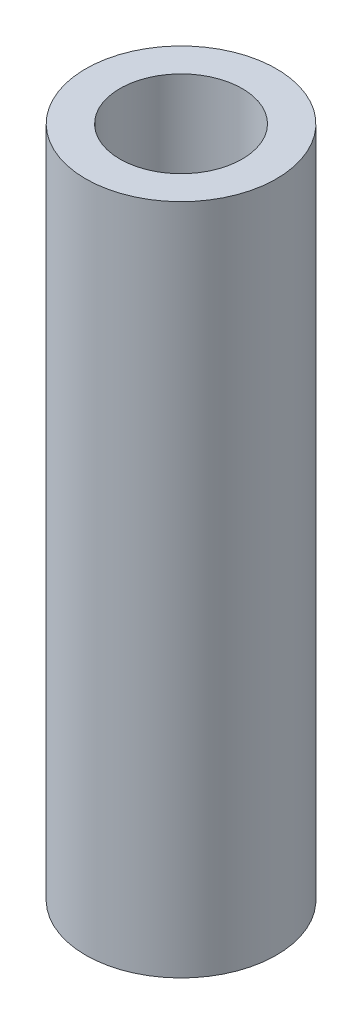
SolidWorks part; units mm, degrees
material "ABS"
ref_plane "Front Plane" through (0, 0, 0) normal (0, 0, 1) x (1, 0, 0)
ref_plane "Top Plane" through (0, 0, 0) normal (0, 1, 0) x (1, 0, 0)
ref_plane "Right Plane" through (0, 0, 0) normal (1, 0, 0) x (0, 0, -1)
sketch "Sketch1" plane through (0, 0, 0) normal (0, 1, 0) x (1, 0, 0)
  circle A0 centre (0, 0) radius 17.875
  circle A1 centre (0, 0) radius 27.875
  dimension "D1" = 35.75
  dimension "D2" = 55.75
extrude "Boss-Extrude1" add sketch "Sketch1" along normal blind 196.5
sketch "Sketch2" plane through (0, 0, 0) normal (1, 0, 0) x (0, 0, -1)
  line L0 (17.875, 196.5) -> (-17.875, 196.5) construction
  circle A0 centre (0, 131.8) radius 9.94
  circle A1 centre (0, 80.8) radius 9.94
  circle A2 centre (0, 29.8) radius 9.94
  dimension "D1" = 19.88
  dimension "D2" = 19.88
  dimension "D3" = 19.88
  dimension "D4" = 64.7
  dimension "D5" = 51
  dimension "D6" = 51
extrude "Cut-Extrude1" cut sketch "Sketch2" against normal through all
